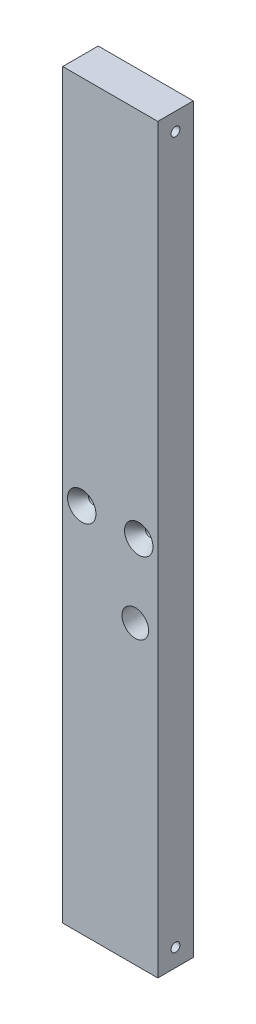
SolidWorks part; units mm, degrees
material "Beech"
ref_plane "Front Plane" through (0, 0, 0) normal (0, 0, 1) x (1, 0, 0)
ref_plane "Top Plane" through (0, 0, 0) normal (0, 1, 0) x (1, 0, 0)
ref_plane "Right Plane" through (0, 0, 0) normal (1, 0, 0) x (0, 0, -1)
sketch "Sketch1" plane through (0, 0, 0) normal (0, 0, 1) x (1, 0, 0)
  line L1 (-6.0809, 0) -> (-40.0809, 0) construction
  line L2 (-40.0809, -132.7) -> (-6.0809, -132.7)
  line L3 (-40.0809, -132.7) -> (-40.0809, 132.7)
  line L5 (-6.0809, -132.7) -> (-6.0809, 132.7)
  line L6 (-40.0809, 132.7) -> (-6.0809, 132.7)
  dimension "D1" = 34
  dimension "D2" = 12.7
extrude "Boss-Extrude1" add sketch "Sketch1" against normal blind 12.7
hole_wizard "3/8 (0.375) Diameter Hole1" positions "Sketch2" profile "Sketch3" hole size "3/8" standard "ANSI Inch" end condition through all
sketch "Sketch2" plane through (0, 0, 0) normal (0, 0, 1) x (1, 0, 0)
  point P0 (-14.118, -26.7327)
sketch "Sketch3" plane through (-14.118, -26.7327, 0) normal (1, 0, 0) x (0, -1, 0)
  line L0 (0, 0) -> (0, 12.7)
  line L1 (0, 12.7) -> (4.7625, 12.7)
  line L2 (4.7625, 12.7) -> (4.7625, 0)
  line L5 (4.7625, 0) -> (0, 0)
  line L11 (0, -6.35) -> (0, 107.95) construction
  dimension "Thru Hole Dia." = 9.525
  dimension "Thru Hole Depth" = 12.7
hole_wizard "Hole1" positions "Sketch4" profile "Sketch5" legacy
sketch "Sketch4" plane through (12.9191, 0, 155.0243) normal (1, 0, 0) x (0, -1, 0)
  line L21 (0, 109.0243) -> (0, 155.0243) construction
  point P37 (126.35, 161.3743)
  point P42 (146.0833, 4.0743)
  point P44 (172.1667, 4.0743)
  point P63 (126.35, 34.5243)
  point P65 (126.35, 130.9243)
  point P76 (-172.1667, 4.0743)
  point P77 (-146.0833, 4.0743)
  point P78 (-126.35, 34.5243)
  point P79 (-126.35, 130.9243)
  point P80 (-126.35, 161.3743)
sketch "Sketch5" plane through (12.9191, -126.35, -6.35) normal (0, 1, 0) x (0, 0, -1)
  line L0 (0, 0) -> (0, 32.7039)
  line L1 (0, 32.7039) -> (1.5875, 31.75)
  line L2 (1.5875, 31.75) -> (1.5875, 4.0177)
  line L3 (1.5875, 4.0177) -> (5.08, 0)
  line L4 (5.08, 0) -> (0, 0)
  line L5 (0, -14.3089) -> (0, 102.4216) construction
  line L6 (0, 32.7039) -> (-1.5875, 31.75) construction
  line L7 (-1.5875, 4.0177) -> (-5.08, 0) construction
  dimension "Diameter" = 3.175
  dimension "Depth" = 31.75
  dimension "C-Sink Diameter" = 10.16
  dimension "C-Sink Angle" = 82
  dimension "Drill Angle" = 118
hole_wizard "Hole3" positions "Sketch7" profile "Sketch8" legacy
sketch "Sketch7" plane through (-195.3677, 0, 0) normal (0, 0, 1) x (0, -1, 0)
  line L0 (0, 155.2867) -> (0, 189.2867) construction
  line L9 (0, 189.2867) -> (0, 182.4867)
  line L10 (0, 182.4867) -> (0, 175.6867)
  line L11 (0, 175.6867) -> (0, 168.8867)
  line L12 (0, 168.8867) -> (0, 162.0867)
  line L13 (0, 162.0867) -> (0, 155.2867)
  point P26 (0, 182.4867)
  point P32 (0, 162.0867)
sketch "Sketch8" plane through (-33.2809, 0, 0) normal (1, 0, 0) x (0, -1, 0)
  line L0 (0, 0) -> (0, 32.7039)
  line L1 (0, 32.7039) -> (1.5875, 31.75)
  line L2 (1.5875, 31.75) -> (1.5875, 4.0177)
  line L3 (1.5875, 4.0177) -> (5.08, 0)
  line L4 (5.08, 0) -> (0, 0)
  line L5 (0, -14.3089) -> (0, 102.4216) construction
  line L6 (0, 32.7039) -> (-1.5875, 31.75) construction
  line L7 (-1.5875, 4.0177) -> (-5.08, 0) construction
  dimension "Diameter" = 3.175
  dimension "Depth" = 31.75
  dimension "C-Sink Diameter" = 10.16
  dimension "C-Sink Angle" = 82
  dimension "Drill Angle" = 118
hole_wizard "Hole4" positions "Sketch9" profile "Sketch10" legacy
sketch "Sketch9" plane through (-52.7809, 0, 155.0243) normal (-1, 0, 0) x (0, 1, 0)
  line L12 (0, 0) -> (0, 155.0243) construction
  point P0 (-207.775, 333.0214)
  point P3 (-207.775, 225.489)
  point P6 (-207.775, 137.4243)
  point P9 (-172.1667, 4.0743)
  point P12 (-146.0833, 4.0743)
  point P15 (-94.6, 161.3743)
  point P18 (0, 161.3743)
  point P21 (94.6, 161.3743)
  point P24 (146.0833, 4.0743)
  point P27 (172.1667, 4.0743)
  point P30 (207.775, 137.4243)
  point P33 (207.775, 225.489)
  point P36 (207.775, 333.0214)
  point P39 (166.7958, 301.9704)
  point P42 (40.9792, 301.9704)
  point P45 (-40.9792, 301.9704)
  point P48 (-166.7958, 301.9704)
  point P51 (0, 193.1243)
  point P54 (0, 301.9704)
  point P57 (0, 412.3664)
  point P80 (-126.35, 106.8243)
  point P82 (-126.35, 58.6243)
  point P96 (126.35, 58.6243)
  point P97 (126.35, 106.8243)
sketch "Sketch10" plane through (-52.7809, -207.775, -177.9971) normal (0, 1, 0) x (0, 0, 1)
  line L0 (0, 0) -> (0, 32.7039)
  line L1 (0, 32.7039) -> (1.5875, 31.75)
  line L2 (1.5875, 31.75) -> (1.5875, 4.0177)
  line L3 (1.5875, 4.0177) -> (5.08, 0)
  line L4 (5.08, 0) -> (0, 0)
  line L5 (0, -14.3089) -> (0, 102.4216) construction
  line L6 (0, 32.7039) -> (-1.5875, 31.75) construction
  line L7 (-1.5875, 4.0177) -> (-5.08, 0) construction
  dimension "Diameter" = 3.175
  dimension "Depth" = 31.75
  dimension "C-Sink Diameter" = 10.16
  dimension "C-Sink Angle" = 82
  dimension "Drill Angle" = 118
